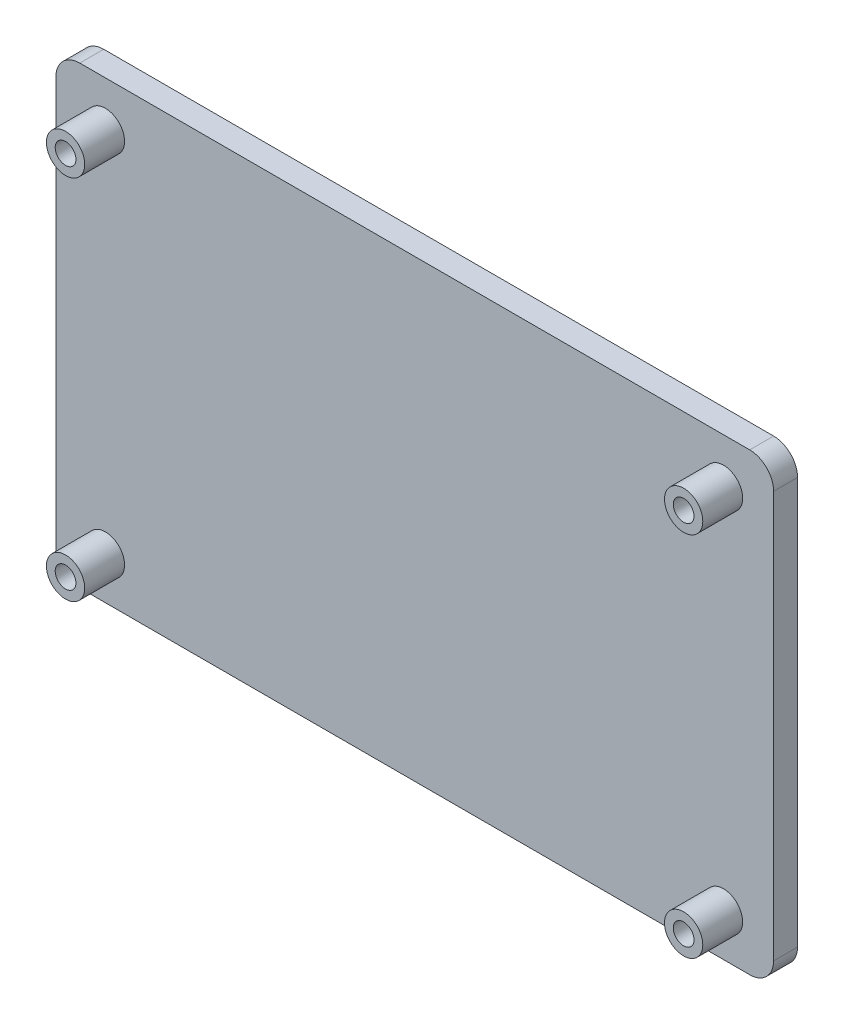
SolidWorks part; units mm, degrees
ref_plane "前视基准面" through (0, 0, 0) normal (0, 0, 1) x (1, 0, 0)
ref_plane "上视基准面" through (0, 0, 0) normal (0, 1, 0) x (1, 0, 0)
ref_plane "右视基准面" through (0, 0, 0) normal (1, 0, 0) x (0, 0, -1)
sketch "草图3" plane through (0, 0, 0) normal (0, 0, 1) x (1, 0, 0)
  line L1 (-43.7179, 29.7031) -> (40.2821, 29.7031)
  line L2 (-46.7179, 26.7031) -> (-46.7179, -24.2969)
  line L3 (-43.7179, -27.2969) -> (40.2821, -27.2969)
  line L4 (43.2821, 26.7031) -> (43.2821, -24.2969)
  circle A1 centre (37, 24) radius 2.4
  circle A2 centre (37, -22) radius 2.4
  circle A4 centre (-40.5, 24) radius 2.4
  circle A5 centre (-40.5, -22) radius 2.4
  circle A6 centre (-40.5, 24) radius 1.3
  circle A7 centre (37, 24) radius 1.3
  circle A8 centre (37, -22) radius 1.3
  circle A9 centre (-40.5, -22) radius 1.3
  arc A10 (-46.7179, 26.7031) -> (-43.7179, 29.7031) centre (-43.7179, 26.7031) cw
  arc A11 (43.2821, 26.7031) -> (40.2821, 29.7031) centre (40.2821, 26.7031) ccw
  arc A12 (43.2821, -24.2969) -> (40.2821, -27.2969) centre (40.2821, -24.2969) cw
  arc A13 (-43.7179, -27.2969) -> (-46.7179, -24.2969) centre (-43.7179, -24.2969) cw
  point P4 (-143.786, -120.7562)
  point P5 (38.0033, -22)
  point P15 (-40.5, -22.8867)
  point P17 (0, 0)
  point P19 (36.1102, 24)
  point P22 (-46.7179, 29.7031)
  point P25 (43.2821, 29.7031)
  point P31 (-46.7179, -27.2969)
  point P32 (0, 0)
  point P33 (0, 0)
  point P34 (0, 0)
  point P35 (0, 0)
  dimension "D3" = 3
  dimension "D4" = 3
  dimension "D1" = 90
  dimension "D2" = 57
extrude "凸台-拉伸5" add sketch "草图3" along normal blind 5.0004 contours A4 A6 region at (-42.8321, 24, 0)
extrude "凸台-拉伸6" add sketch "草图3<8>" along normal blind 5 separate body contours A1 A7 region at (34.6679, 24, 0)
sketch "草图3<8>" plane through (0, 0, 0) normal (0, 0, 1) x (1, 0, 0) same geometry as "草图3"
extrude "凸台-拉伸7" add sketch "草图3<9>" along normal blind 5 separate body contours A2 A8 region at (34.6679, -22, 0)
sketch "草图3<9>" plane through (0, 0, 0) normal (0, 0, 1) x (1, 0, 0) same geometry as "草图3"
extrude "凸台-拉伸8" add sketch "草图3<10>" along normal blind 5 separate body contours A9 | A5
sketch "草图3<10>" plane through (0, 0, 0) normal (0, 0, 1) x (1, 0, 0) same geometry as "草图3"
extrude "凸台-拉伸12" add sketch "草图3<17>" against normal blind 3 contours A13 L3 A12 L4 A11 L1 A10 L2 A5 A4 A2 A1 | A4 | A5 | A7 | A1 | A2 | A6 | A9 | A8 region at (-1.7174, 1.206, 0)
sketch "草图3<17>" plane through (0, 0, 0) normal (0, 0, 1) x (1, 0, 0) same geometry as "草图3"
